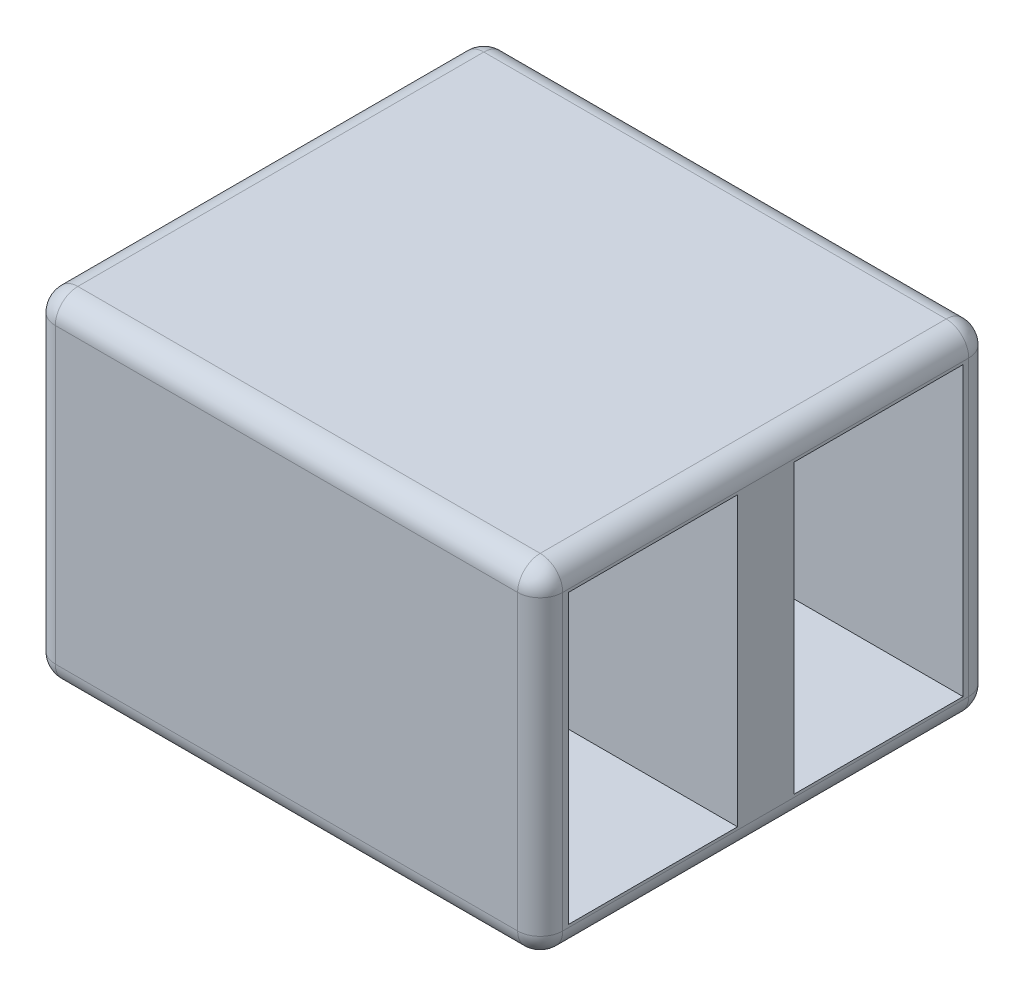
SolidWorks part; units mm, degrees
material "Custom Plastic"
ref_plane "Front Plane" through (0, 0, 0) normal (0, 0, 1) x (1, 0, 0)
ref_plane "Top Plane" through (0, 0, 0) normal (0, 1, 0) x (1, 0, 0)
ref_plane "Right Plane" through (0, 0, 0) normal (1, 0, 0) x (0, 0, -1)
sketch "Sketch1" plane through (0, 0, 0) normal (0, 1, 0) x (1, 0, 0)
  line L1 (-22.5, -20) -> (22.5, -20)
  line L2 (-22.5, -20) -> (-22.5, 20)
  line L3 (-22.5, 20) -> (22.5, 20)
  line L4 (22.5, -20) -> (22.5, 20)
  line L5 (-22.5, -20) -> (22.5, 20) construction
  line L6 (-22.5, 20) -> (22.5, -20) construction
  point P0 (0, 0)
  dimension "D1" = 45
  dimension "D2" = 40
extrude "Boss-Extrude1" add sketch "Sketch1" along normal blind 15 and the other way blind 15 contours L2 L3 L4 L1
sketch "Sketch2" plane through (0, 0, 0) normal (0, 1, 0) x (1, 0, 0)
  line L0 (-1000, 0) -> (49000, 0) construction
  line L1 (22.5, -20) -> (22.5, 20) construction
  line L2 (22.5, 17.5) -> (-15.5, 17.5)
  line L3 (22.5, 17.5) -> (22.5, 2.5)
  line L4 (22.5, 2.5) -> (-15.5, 2.5)
  line L5 (-15.5, 17.5) -> (-15.5, 2.5)
  line L6 (-15.5, -17.5) -> (-15.5, -2.5)
  line L7 (22.5, -2.5) -> (-15.5, -2.5)
  line L8 (22.5, -17.5) -> (22.5, -2.5)
  line L9 (22.5, -17.5) -> (-15.5, -17.5)
  dimension "D1" = 15
  dimension "D2" = 38
  dimension "D3" = 5
extrude "Cut-Extrude1" cut sketch "Sketch2" against normal blind 12.75 and the other way blind 12.75
fillet "Fillet1" radius 13 4 edges at (-15.5, -12.75, -10) (-15.5, 12.75, -10) (-15.5, 12.75, 10) (-15.5, -12.75, 10)
fillet "Fillet2" radius 2 12 edges at (-22.5, -15, 0) (-22.5, 0, -20) (-22.5, 15, 0) (-22.5, 0, 20) (22.5, 0, -20) (22.5, 0, 20) (0, -15, 20) (22.5, -15, 0) (0, -15, -20) (0, 15, -20) (0, 15, 20) (22.5, 15, 0)
sketch "Sketch3" plane through (0, 0, 0) normal (0, 1, 0) x (1, 0, 0)
  line L0 (-22.5, 0) -> (-32.5, 0)
  line L1 (-22.5, -18) -> (-22.5, 18) construction
  line L2 (-32.5, 0) -> (-22.5, 5)
  line L3 (-22.5, 5) -> (-22.5, 0)
  dimension "D1" = 5
  dimension "D2" = 10
revolve "Revolve1" add sketch "Sketch3" angle 360 about L0
